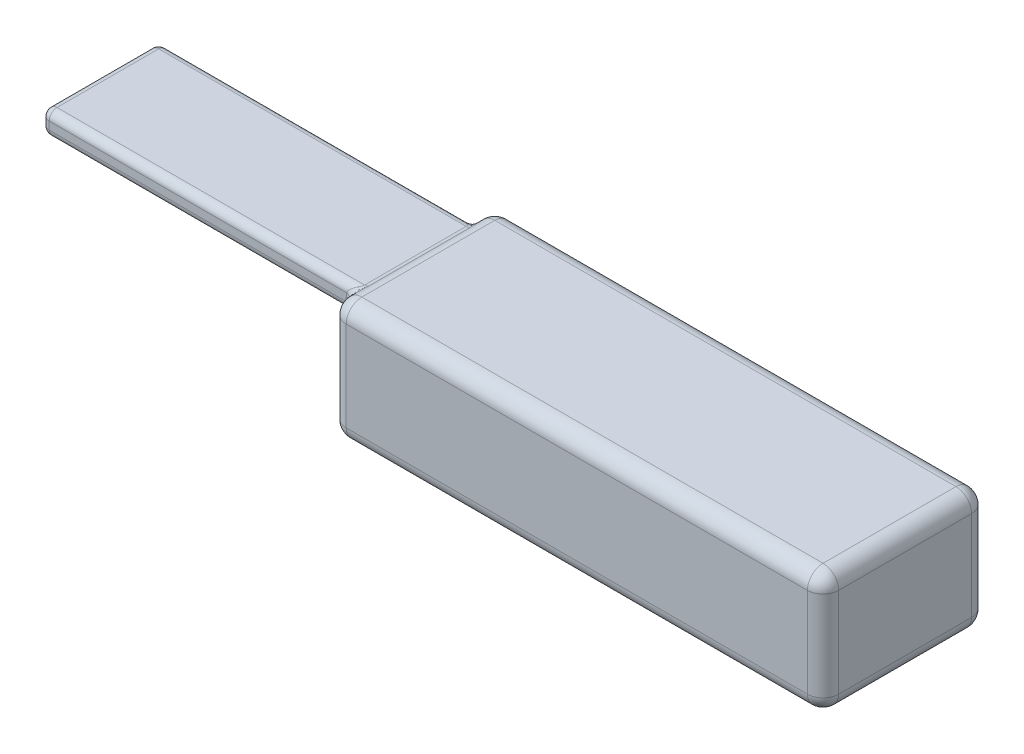
SolidWorks part; units mm, degrees
ref_plane "Front Plane" through (0, 0, 0) normal (0, 0, 1) x (1, 0, 0)
ref_plane "Top Plane" through (0, 0, 0) normal (0, 1, 0) x (1, 0, 0)
ref_plane "Right Plane" through (0, 0, 0) normal (1, 0, 0) x (0, 0, -1)
sketch "Sketch1" plane through (0, 0, 0) normal (0, 0, 1) x (1, 0, 0)
  line L1 (0, 0) -> (63, 0)
  line L2 (0, 0) -> (0, 15.5)
  line L3 (0, 15.5) -> (63, 15.5)
  line L4 (63, 0) -> (63, 15.5)
  dimension "D1" = 63
  dimension "D2" = 15.5
extrude "Boss-Extrude1" add sketch "Sketch1" along normal blind 21
sketch "Sketch2" plane through (0, 0, 0) normal (-1, 0, 0) x (0, 0, 1)
  line L1 (3, 15) -> (18, 15)
  line L2 (3, 15) -> (3, 12)
  line L3 (3, 12) -> (18, 12)
  line L4 (18, 15) -> (18, 12)
  line L5 (10.5, 0) -> (10.5, 20.643) construction
  line L6 (21, 0) -> (0, 0) construction
  line L8 (21, 15.5) -> (0, 15.5) construction
  dimension "D1" = 15
  dimension "D2" = 3
  dimension "D3" = 0.5
extrude "Boss-Extrude2" add sketch "Sketch2" along normal blind 40
fillet "Fillet1" radius 2 12 edges at (0, 7.75, 0) (0, 0, 10.5) (31.5, 0, 0) (63, 0, 10.5) (63, 7.75, 0) (63, 15.5, 10.5) (0, 15.5, 10.5) (31.5, 15.5, 0) (31.5, 15.5, 21) (63, 7.75, 21) (31.5, 0, 21) (0, 7.75, 21)
fillet "Fillet2" radius 1 14 edges at (0.1771, 14.3229, 18) (0, 12.75, 18) (-20, 12, 18) (0, 12, 10.5) (-40, 13.5, 18) (-40, 12, 10.5) (-40, 13.5, 3) (-20, 12, 3) (0, 12.75, 3) (0.1771, 14.3229, 3) (-40, 15, 10.5) (-19.6614, 15, 3) (0.6771, 15, 10.5) (-19.6614, 15, 18)
